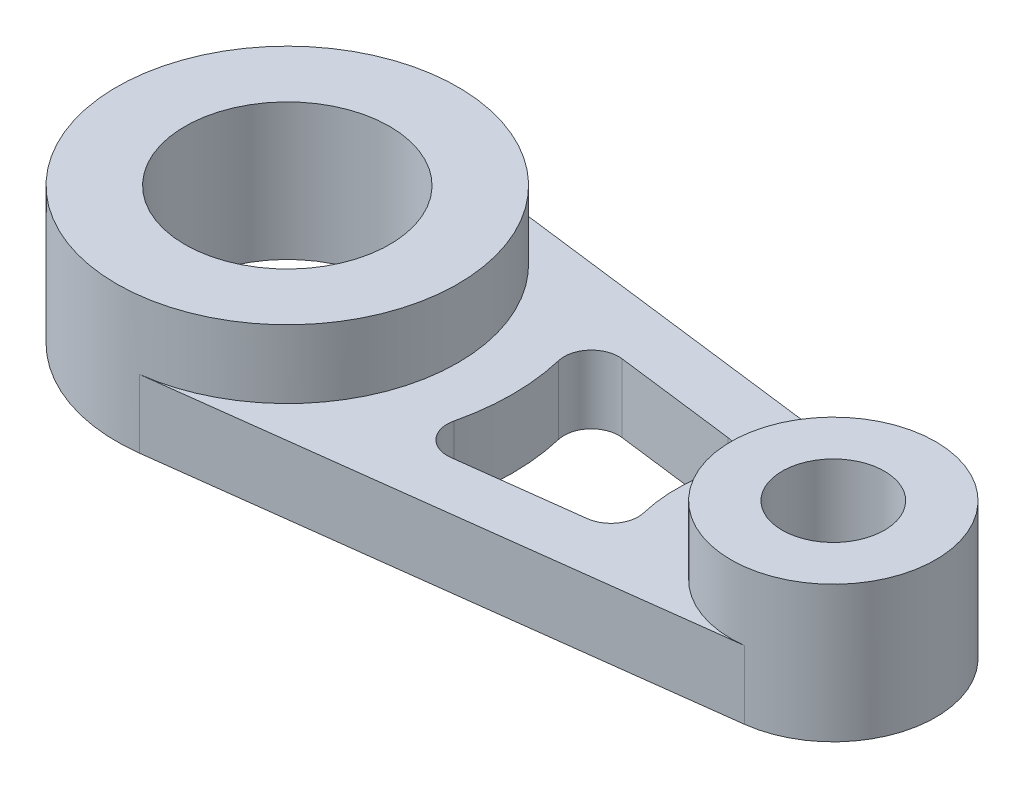
SolidWorks part; units mm, degrees
ref_plane "Front Plane" through (0, 0, 0) normal (0, 0, 1) x (1, 0, 0)
ref_plane "Top Plane" through (0, 0, 0) normal (0, 1, 0) x (1, 0, 0)
ref_plane "Right Plane" through (0, 0, 0) normal (1, 0, 0) x (0, 0, -1)
sketch "Sketch1" plane through (0, 0, 0) normal (0, 1, 0) x (1, 0, 0)
  line L0 (3.125, 24.8039) -> (81.875, 14.8824)
  line L1 (3.125, -24.8039) -> (81.875, -14.8824)
  circle A0 centre (0, 0) radius 15
  circle A1 centre (0, 0) radius 25
  circle A2 centre (80, 0) radius 7.5
  circle A3 centre (80, 0) radius 15
  point P11 (0, 0)
  dimension "D1" = 15
  dimension "D2" = 30
  dimension "D3" = 50
  dimension "D4" = 30
  dimension "D5" = 80
extrude "Boss-Extrude1" add sketch "Sketch1" along normal blind 10 contours A1 A0 | A3 A2 | A3 L0 A1 L1 region at (43.3004, 0, 0) region at (18.2197, 0, -16.0682) region at (90.9318, 0, -9.6409)
extrude "Boss-Extrude2" add sketch "Sketch1<3>" along normal blind 20 contours A1 A0 | A3 A2 region at (18.2197, 0, -16.0682) region at (90.9318, 0, -9.6409)
sketch "Sketch1<3>" plane through (0, 0, 0) normal (0, 1, 0) x (1, 0, 0) same geometry as "Sketch1"
sketch "Sketch2" plane through (0, 10, 0) normal (0, 1, 0) x (1, 0, 0)
  line L8 (30.1874, -13.3311) -> (59.1379, -9.6837)
  line L9 (59.1379, 9.6837) -> (30.1874, 13.3311)
  line L10 (36.4943, -12.5365) -> (54.2526, -10.2992)
  line L11 (54.2526, 10.2992) -> (36.4943, 12.5365)
  arc A6 (57.6411, 5.3927) -> (54.2526, 10.2992) centre (53.7526, 6.3306) ccw
  arc A7 (54.2526, -10.2992) -> (57.6411, -5.3927) centre (53.7526, -6.3306) ccw
  arc A8 (59.1379, 9.6837) -> (59.1379, -9.6837) centre (80, 0) ccw
  arc A9 (30.1874, -13.3311) -> (30.1874, 13.3311) centre (0, 0) ccw
  arc A10 (57.6411, 5.3927) -> (57.6411, -5.3927) centre (80, 0) ccw
  arc A11 (32.103, -7.6417) -> (32.103, 7.6417) centre (0, 0) ccw
  arc A12 (36.4943, -12.5365) -> (32.103, -7.6417) centre (35.9943, -8.5679) cw
  arc A13 (36.4943, 12.5365) -> (32.103, 7.6417) centre (35.9943, 8.5679) ccw
  dimension "D2" = 4
  dimension "D1" = 8
extrude "Cut-Extrude1" cut sketch "Sketch2" against normal blind 20
